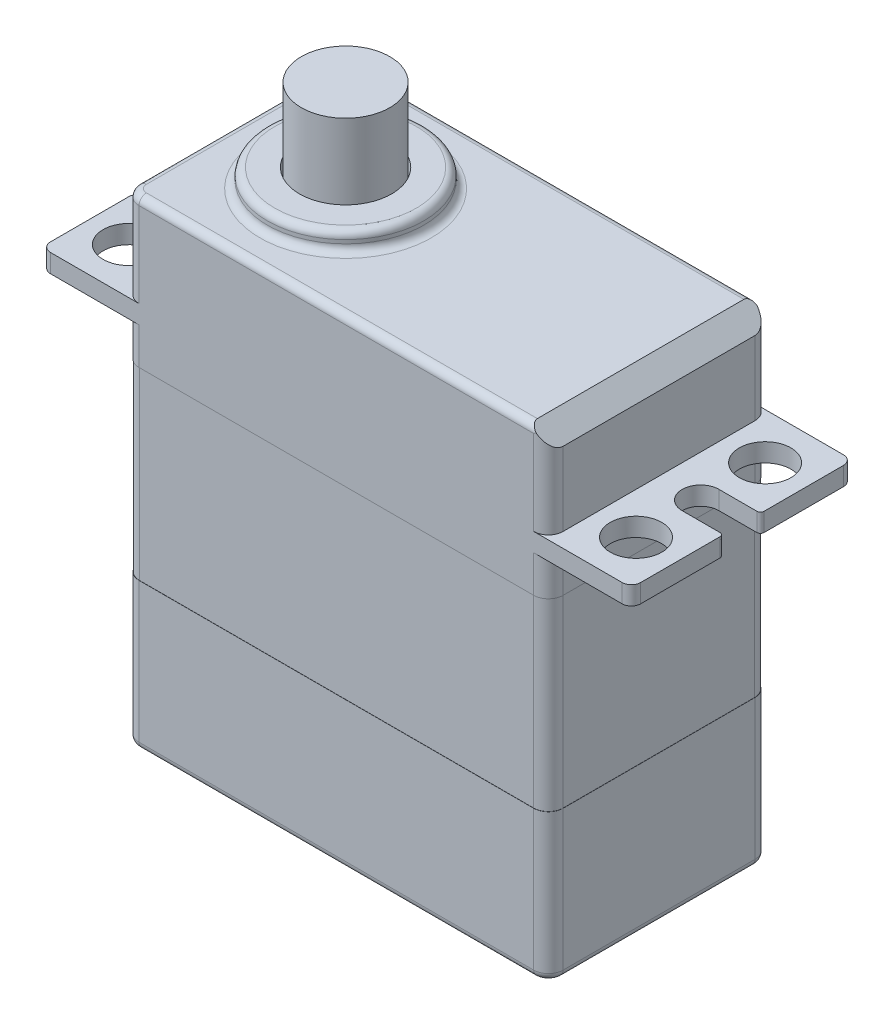
SolidWorks part; units mm, degrees
ref_plane "Plano frontal" through (0, 0, 0) normal (0, 0, 1) x (1, 0, 0)
ref_plane "Plano superior" through (0, 0, 0) normal (0, 1, 0) x (1, 0, 0)
ref_plane "Plano direito" through (0, 0, 0) normal (1, 0, 0) x (0, 0, -1)
sketch "Esboço1" plane through (0, 0, 0) normal (0, 1, 0) x (1, 0, 0)
  line L1 (-11.5, -6) -> (11.5, -6)
  line L2 (-11.5, -6) -> (-11.5, 6)
  line L3 (-11.5, 6) -> (11.5, 6)
  line L4 (11.5, -6) -> (11.5, 6)
  line L5 (-11.5, -6) -> (11.5, 6) construction
  line L6 (-11.5, 6) -> (11.5, -6) construction
  point P0 (0, 0)
  dimension "D1" = 23
  dimension "D2" = 12
extrude "Ressalto-extrusão1" add sketch "Esboço1" along normal blind 26
ref_plane "Plano1" through (0, 8, 0) normal (0, -1, 0) x (-1, 0, 0)
sketch "Esboço8" plane through (0, 8, 0) normal (0, -1, 0) x (-1, 0, 0)
  line L0 (11.49, 5.99) -> (-11.49, 5.99)
  line L1 (11.5, 6) -> (-11.5, 6)
  line L2 (11.5, 6) -> (11.5, -6)
  line L3 (11.5, -6) -> (-11.5, -6)
  line L4 (-11.5, 6) -> (-11.5, -6)
  line L5 (-11.49, 5.99) -> (-11.49, -5.99)
  line L6 (11.49, -5.99) -> (-11.49, -5.99)
  line L7 (11.49, 5.99) -> (11.49, -5.99)
  dimension "D1" = 0.01
extrude "Corte-extrusão3" cut sketch "Esboço8" against normal blind 10
sketch "Esboço2" plane through (0, 26, 0) normal (0, 1, 0) x (1, 0, 0)
  line L0 (11.5, 6) -> (-11.5, 6) construction
  line L1 (-11.5, 6) -> (-11.5, -6) construction
  circle A0 centre (-5.5, 0) radius 4.2396
  dimension "D1" = 6
  dimension "D2" = 6
extrude "Ressalto-extrusão2" add sketch "Esboço2" along normal blind 1
sketch "Esboço3" plane through (0, 27, 0) normal (0, 1, 0) x (1, 0, 0)
  circle A0 centre (-5.5, 0) radius 2.5
  dimension "D1" = 5
extrude "Corte-extrusão1" cut sketch "Esboço3" against normal blind 1
sketch "Esboço4" plane through (0, 26, 0) normal (0, 1, 0) x (1, 0, 0)
  circle A0 centre (-5.5, 0) radius 2.4
  dimension "D1" = 4.8
extrude "Ressalto-extrusão3" add sketch "Esboço4" along normal blind 5
sketch "Esboço5" plane through (11.5, 0, 0) normal (1, 0, 0) x (0, 0, -1)
  line L0 (-6, 26) -> (-6, 18) construction
  line L1 (-6, 21) -> (6, 21)
  line L2 (-6, 21) -> (-6, 20)
  line L3 (-6, 20) -> (6, 20)
  line L4 (6, 21) -> (6, 20)
  line L5 (6, 26) -> (6, 18) construction
  line L6 (-6, 0) -> (6, 0) construction
  dimension "D1" = 1
  dimension "D2" = 20
extrude "Ressalto-extrusão4" add sketch "Esboço5" along normal blind 4.5
sketch "Esboço6" plane through (0, 21, 0) normal (0, 1, 0) x (1, 0, 0)
  line L0 (16, 6) -> (11.5, 6) construction
  line L1 (16, 6) -> (16, -6) construction
  line L2 (16, 0) -> (11.5, 0) construction
  line L3 (11.5, -6) -> (11.5, 6) construction
  line L4 (13.75, 6) -> (13.75, -6) construction
  line L5 (16, -6) -> (11.5, -6) construction
  line L6 (13.75, 1) -> (16, 1)
  line L7 (13.75, -1) -> (16, -1)
  line L8 (16, -1) -> (16, 1)
  circle A0 centre (13.75, 3.5) radius 1.4
  circle A1 centre (13.75, -3.5) radius 1.4
  arc A2 (13.75, 1) -> (13.75, -1) centre (13.75, 0) ccw
  dimension "D1" = 2.8
  dimension "D2" = 2.5
  dimension "D3" = 2
extrude "Corte-extrusão2" cut sketch "Esboço6" against normal blind 4.5
fillet "Filete1" radius 0.5 2 edges at (16, 20.5, -6) (16, 20.5, 6)
fillet "Filete2" radius 0.2 2 edges at (16, 20.5, 1) (16, 20.5, -1)
mirror "Espelhar1" about plane through (0, 0, 0) normal (1, 0, 0) of "Filete2", "Filete1", "Corte-extrusão2", "Ressalto-extrusão4"
fillet "Filete3" radius 0.8 16 edges at (11.5, 4, 6) (-11.5, 4, 6) (-11.5, 4, -6) (11.5, 4, -6) (-11.49, 13, 5.99) (11.49, 13, 5.99) (11.49, 13, -5.99) (-11.49, 13, -5.99)
chamfer "Chanfro1" distance 1 angle 45 1 edges at (11.5, 26, 0) tangent propagation no
fillet "Filete4" radius 0.4 13 edges at (-0.1, 26, -6) (-11.2657, 26, -5.7657) (-11.5, 26, 0) (-11.2657, 26, 5.7657) (-0.1, 26, 6) (-11.5, 0, 0) (0, 0, -6) (11.5, 0, 0) (0, 0, 6) (-11.2657, 0, 5.7657) (-11.2657, 0, -5.7657) (11.2657, 0, -5.7657) (11.2657, 0, 5.7657)
fillet "Filete5" radius 0.4 1 edges at (-5.5, 27, 4.2396)
fillet "Filete6" radius 0.4 1 edges at (-5.5, 26, -4.2396)
